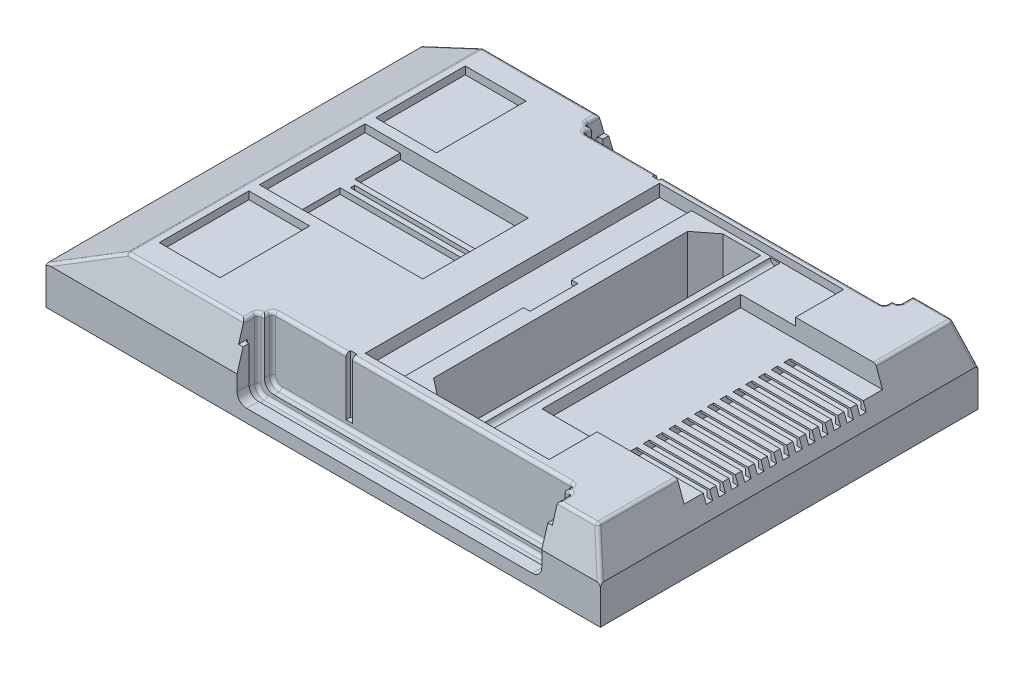
SolidWorks part; units mm, degrees
ref_plane "Front Plane" through (0, 0, 0) normal (0, 0, 1) x (1, 0, 0)
ref_plane "Top Plane" through (0, 0, 0) normal (0, 1, 0) x (1, 0, 0)
ref_plane "Right Plane" through (0, 0, 0) normal (1, 0, 0) x (0, 0, -1)
sketch "Sketch1" plane through (0, 0, 0) normal (0, 1, 0) x (1, 0, 0)
  line L1 (-219.964, -149.86) -> (0, -149.86)
  line L2 (-219.964, -149.86) -> (-219.964, 0)
  line L3 (-219.964, 0) -> (0, 0)
  line L4 (0, -149.86) -> (0, 0)
  dimension "D1" = 149.86
  dimension "D2" = 219.964
ref_plane "MiddleTop" through (0, 14.986, 0) normal (0, 1, 0) x (1, 0, 0)
sketch "Sketch2" plane through (0, 14.986, 0) normal (0, 1, 0) x (1, 0, 0)
  line L1 (0, 0) -> (-219.964, 0)
  line L2 (0, 0) -> (0, -149.86)
  line L3 (0, -149.86) -> (-219.964, -149.86)
  line L4 (-219.964, 0) -> (-219.964, -149.86)
extrude "Boss-Extrude1" add sketch "Sketch1" along normal blind 14.986
ref_plane "Plane2" through (0, 30.48, 0) normal (0, 1, 0) x (1, 0, 0)
sketch "Sketch3" plane through (0, 30.48, 0) normal (0, 1, 0) x (1, 0, 0)
  line L0 (0, -149.86) -> (-219.964, -149.86) construction
  line L1 (-192.024, -4.572) -> (-5.588, -4.572)
  line L2 (-192.024, -4.572) -> (-192.024, -145.288)
  line L3 (-192.024, -145.288) -> (-5.588, -145.288)
  line L4 (-5.588, -4.572) -> (-5.588, -145.288)
  line L5 (-219.964, 0) -> (-219.964, -149.86) construction
  line L6 (0, 0) -> (0, -149.86) construction
  dimension "D1" = 140.716
  dimension "D2" = 4.572
  dimension "D3" = 27.94
  dimension "D4" = 5.588
loft "Loft1" add profiles "Sketch2", "Sketch3" connector at (-219.964, 14.986, 149.86) connector at (-192.024, 30.48, 145.288)
sketch "Sketch4" plane through (0, 30.48, 0) normal (0, 1, 0) x (1, 0, 0)
  line L0 (-192.024, -145.288) -> (-5.588, -145.288) construction
  line L1 (-189.23, -135.636) -> (-165.1, -135.636)
  line L2 (-189.23, -135.636) -> (-189.23, -100.076)
  line L3 (-189.23, -100.076) -> (-165.1, -100.076)
  line L4 (-165.1, -135.636) -> (-165.1, -100.076)
  line L5 (-192.024, -4.572) -> (-192.024, -145.288) construction
  line L6 (-5.588, -4.572) -> (-192.024, -4.572) construction
  line L7 (-189.23, -49.784) -> (-165.1, -49.784)
  line L8 (-189.23, -49.784) -> (-189.23, -14.224)
  line L9 (-189.23, -14.224) -> (-165.1, -14.224)
  line L10 (-165.1, -49.784) -> (-165.1, -14.224)
  point P12 (-177.165, -14.224)
  dimension "D1" = 35.56
  dimension "D2" = 24.13
  dimension "D3" = 9.652
  dimension "D4" = 2.794
  dimension "D5" = 24.13
  dimension "D6" = 35.56
  dimension "D7" = 2.794
  dimension "D8" = 9.652
sketch "Sketch5" plane through (0, 30.48, 0) normal (0, 1, 0) x (1, 0, 0)
  line L0 (-189.23, -100.076) -> (-165.1, -100.076) construction
  line L1 (-189.23, -95.885) -> (-124.46, -95.885)
  line L2 (-189.23, -95.885) -> (-189.23, -53.975)
  line L3 (-189.23, -53.975) -> (-124.46, -53.975)
  line L4 (-124.46, -95.885) -> (-124.46, -53.975)
  line L5 (-192.024, -4.572) -> (-192.024, -145.288) construction
  dimension "D1" = 41.91
  dimension "D2" = 4.191
  dimension "D3" = 2.794
  dimension "D4" = 64.77
extrude "Cut-Extrude1" cut sketch "Sketch4" against normal blind 3.048
extrude "Cut-Extrude2" cut sketch "Sketch5" against normal blind 3.048
ref_plane "Plane3" through (0, 25.146, 0) normal (0, 1, 0) x (1, 0, 0)
sketch "Sketch6" plane through (0, 25.146, 0) normal (0, 1, 0) x (1, 0, 0)
  line L0 (-189.23, -53.975) -> (-189.23, -95.885) construction
  line L1 (-175.26, -72.0598) -> (-124.46, -72.0598)
  line L2 (-175.26, -72.0598) -> (-175.26, -77.851)
  line L3 (-175.26, -77.851) -> (-124.46, -77.851)
  line L4 (-124.46, -72.0598) -> (-124.46, -77.851)
  line L5 (-189.23, -95.885) -> (-124.46, -95.885) construction
  dimension "D1" = 50.8
  dimension "D2" = 13.97
  dimension "D3" = 5.7912
  dimension "D4" = 18.034
sketch "Sketch10" plane through (0, 30.48, 0) normal (0, 1, 0) x (1, 0, 0)
  line L6 (-219.964, -149.86) -> (0, -149.86) construction
  line L9 (-144.145, -145.1356) -> (-145.923, -145.1356)
  line L10 (-145.923, -145.1356) -> (-145.923, -139.8016)
  line L11 (-145.923, -139.8016) -> (-143.383, -139.8016)
  line L12 (-143.383, -139.8016) -> (-143.383, -136.5758)
  line L13 (-143.383, -136.5758) -> (-24.003, -136.5758)
  line L14 (-24.003, -136.5758) -> (-24.003, -139.8016)
  line L15 (-24.003, -139.8016) -> (-21.463, -139.8016)
  line L16 (-21.463, -139.8016) -> (-21.463, -145.1356)
  line L17 (-21.463, -145.1356) -> (-23.241, -145.1356)
  line L21 (-23.241, -149.86) -> (-144.145, -149.86)
  line L22 (-144.145, -145.1356) -> (-144.145, -149.86)
  line L23 (-23.241, -145.1356) -> (-23.241, -149.86)
  line L24 (0, -149.86) -> (0, 0) construction
  line L25 (-219.964, -74.93) -> (-5.588, -74.93) construction
  line L27 (-219.964, 0) -> (-219.964, -149.86) construction
  line L28 (-5.588, -145.288) -> (-5.588, -4.572) construction
  line L29 (-21.463, -4.7244) -> (-23.241, -4.7244)
  line L30 (-21.463, -10.0584) -> (-21.463, -4.7244)
  line L31 (-24.003, -10.0584) -> (-21.463, -10.0584)
  line L32 (-24.003, -13.2842) -> (-24.003, -10.0584)
  line L33 (-143.383, -13.2842) -> (-24.003, -13.2842)
  line L34 (-143.383, -10.0584) -> (-143.383, -13.2842)
  line L35 (-145.923, -10.0584) -> (-143.383, -10.0584)
  line L36 (-145.923, -4.7244) -> (-145.923, -10.0584)
  line L37 (-144.145, -4.7244) -> (-145.923, -4.7244)
  line L38 (-144.145, -4.7244) -> (-144.145, 0)
  line L39 (-23.241, 0) -> (-144.145, 0)
  line L40 (-23.241, -4.7244) -> (-23.241, 0)
  dimension "D1" = 13.2842
  dimension "D2" = 5.334
  dimension "D3" = 3.2258
  dimension "D4" = 2.54
  dimension "D5" = 124.46
  dimension "D6" = 3.2258
  dimension "D7" = 2.54
  dimension "D8" = 1.778
  dimension "D9" = 5.334
  dimension "D10" = 21.463
  dimension "D11" = 1.778
sketch "Sketch12" plane through (0, 30.48, 0) normal (0, 1, 0) x (1, 0, 0)
  line L1 (-145.923, -10.0584) -> (-21.463, -10.0584)
  line L2 (-145.923, -10.0584) -> (-145.923, -4.7244)
  line L3 (-145.923, -4.7244) -> (-21.463, -4.7244)
  line L4 (-21.463, -10.0584) -> (-21.463, -4.7244)
  line L5 (-145.923, -145.1356) -> (-21.463, -145.1356)
  line L6 (-145.923, -145.1356) -> (-145.923, -139.8016)
  line L7 (-145.923, -139.8016) -> (-21.463, -139.8016)
  line L8 (-21.463, -145.1356) -> (-21.463, -139.8016)
extrude "Cut-Extrude4" cut sketch "Sketch12" against normal blind 27.94
extrude "Cut-Extrude5" cut sketch "Sketch10" against normal blind 25.4
sketch "Sketch14" plane through (0, 30.48, 0) normal (0, 1, 0) x (1, 0, 0)
  line L1 (-145.923, -145.1356) -> (-144.145, -145.1356)
  line L2 (-145.923, -145.1356) -> (-145.923, -149.86)
  line L3 (-145.923, -149.86) -> (-144.145, -149.86)
  line L4 (-144.145, -145.1356) -> (-144.145, -149.86)
  line L5 (-21.463, -145.1356) -> (-23.241, -145.1356)
  line L6 (-21.463, -145.1356) -> (-21.463, -149.86)
  line L7 (-21.463, -149.86) -> (-23.241, -149.86)
  line L8 (-23.241, -145.1356) -> (-23.241, -149.86)
  line L9 (-145.923, -4.7244) -> (-144.145, -4.7244)
  line L10 (-145.923, -4.7244) -> (-145.923, 0)
  line L11 (-145.923, 0) -> (-144.145, 0)
  line L12 (-144.145, -4.7244) -> (-144.145, 0)
  line L13 (-21.463, -4.7244) -> (-23.241, -4.7244)
  line L14 (-21.463, -4.7244) -> (-21.463, 0)
  line L15 (-21.463, 0) -> (-23.241, 0)
  line L16 (-23.241, -4.7244) -> (-23.241, 0)
extrude "Cut-Extrude6" cut sketch "Sketch14" against normal blind 7.366
sketch "Sketch15" plane through (0, 30.48, 0) normal (0, 1, 0) x (1, 0, 0)
  line L0 (-5.588, -145.288) -> (-5.588, -4.572) construction
  line L1 (-110.363, -16.002) -> (-37.338, -16.002)
  line L2 (-110.363, -16.002) -> (-110.363, -132.842)
  line L3 (-110.363, -132.842) -> (-37.338, -132.842)
  line L4 (-37.338, -16.002) -> (-37.338, -35.052)
  line L5 (-5.588, -4.572) -> (-21.463, -4.572) construction
  line L6 (-37.338, -35.052) -> (-59.182, -35.052)
  line L7 (-59.182, -35.052) -> (-59.182, -113.792)
  line L8 (-59.182, -113.792) -> (-37.338, -113.792)
  line L9 (-37.338, -113.792) -> (-37.338, -132.842)
  dimension "D1" = 73.025
  dimension "D2" = 31.75
  dimension "D3" = 116.84
  dimension "D4" = 11.43
  dimension "D5" = 21.844
  dimension "D6" = 78.74
  dimension "D7" = 19.05
extrude "Cut-Extrude7" cut sketch "Sketch15" against normal blind 3.048
sketch "Sketch16" plane through (0, 30.48, 0) normal (0, 1, 0) x (1, 0, 0)
  line L1 (-59.182, -35.052) -> (0.508, -35.052)
  line L2 (-59.182, -35.052) -> (-59.182, -113.792)
  line L3 (-59.182, -113.792) -> (0.508, -113.792)
  line L4 (0.508, -35.052) -> (0.508, -113.792)
  point P7 (0, 0)
  point P9 (0, 0)
  dimension "D1" = 59.69
extrude "Cut-Extrude8" cut sketch "Sketch16" against normal blind 7.62
sketch "Sketch17" plane through (0, 30.48, 0) normal (0, 1, 0) x (1, 0, 0)
  line L0 (-110.363, -132.842) -> (-37.338, -132.842) construction
  line L1 (-110.363, -16.002) -> (-97.663, -16.002)
  line L2 (-110.363, -16.002) -> (-110.363, -132.842)
  line L3 (-110.363, -132.842) -> (-97.663, -132.842)
  line L4 (-97.663, -16.002) -> (-97.663, -63.627)
  line L5 (-97.663, -63.627) -> (-95.123, -63.627)
  line L6 (-95.123, -63.627) -> (-95.123, -82.677)
  line L7 (-95.123, -82.677) -> (-97.663, -82.677)
  line L8 (-97.663, -82.677) -> (-97.663, -132.842)
  dimension "D1" = 12.7
  dimension "D2" = 19.05
  dimension "D3" = 47.625
  dimension "D4" = 2.54
extrude "Cut-Extrude9" cut sketch "Sketch17" against normal blind 4.826
sketch "Sketch18" plane through (0, 30.48, 0) normal (0, 1, 0) x (1, 0, 0)
  line L0 (-83.5048, -17.78) -> (-91.313, -23.876)
  line L1 (-83.5048, -17.78) -> (-68.5188, -17.78)
  line L2 (-91.313, -23.876) -> (-91.313, -124.714)
  line L3 (-83.5048, -130.81) -> (-68.5188, -130.81)
  line L4 (-68.5188, -17.78) -> (-68.5188, -130.81)
  line L5 (-83.5048, -130.81) -> (-91.313, -124.714)
  line L6 (-97.663, -132.842) -> (-37.338, -132.842) construction
  line L8 (-95.123, -82.677) -> (-95.123, -63.627) construction
  dimension "D1" = 14.986
  dimension "D2" = 9.906
  dimension "D3" = 9.906
  dimension "D4" = 14.986
  dimension "D5" = 100.838
  dimension "D6" = 113.03
  dimension "D7" = 2.032
  dimension "D8" = 3.81
extrude "Cut-Extrude10" cut sketch "Sketch18" against normal through all
sketch "Sketch19" plane through (0, 30.48, 0) normal (0, 1, 0) x (1, 0, 0)
  line L0 (0, -149.86) -> (0, 0) construction
  line L1 (-31.75, -42.672) -> (0, -42.672)
  line L2 (-31.75, -42.672) -> (-31.75, -45.212)
  line L3 (-31.75, -45.212) -> (0, -45.212)
  line L4 (0, -42.672) -> (0, -45.212)
  line L5 (-2.8398, -35.052) -> (-59.182, -35.052) construction
  dimension "D1" = 2.54
  dimension "D2" = 31.75
  dimension "D3" = 7.62
extrude "Cut-Extrude11" cut sketch "Sketch19" against normal blind 10.922
pattern_linear "LPattern1" count 13 spacing 5.08 along (0, 0, 1) of "Cut-Extrude11"
ref_plane "Plane5" through (0, 0, 103.632) normal (0, 0, 1) x (1, 0, 0)
sketch "Sketch20" plane through (0, 0, 103.632) normal (0, 0, 1) x (1, 0, 0)
  line L0 (-2.8398, 22.86) -> (-31.75, 22.86) construction
  line L1 (-31.75, 22.098) -> (-3.81, 22.098)
  line L2 (-31.75, 22.098) -> (-31.75, 19.558)
  line L3 (-31.75, 19.558) -> (-3.81, 19.558)
  line L4 (-3.81, 22.098) -> (-3.81, 19.558)
  line L6 (-31.75, 19.558) -> (-31.75, 22.86) construction
  dimension "D1" = 0.762
  dimension "D2" = 2.54
  dimension "D3" = 0
  dimension "D4" = 27.94
extrude "Cut-Extrude12" cut sketch "Sketch20" against normal blind 63.5
sketch "Sketch25" plane through (0, 30.48, 0) normal (0, 1, 0) x (1, 0, 0)
  line L1 (-175.26, -72.0598) -> (-124.46, -72.0598)
  line L2 (-175.26, -72.0598) -> (-175.26, -53.975)
  line L3 (-175.26, -53.975) -> (-124.46, -53.975)
  line L4 (-124.46, -72.0598) -> (-124.46, -53.975)
  line L5 (-175.26, -77.851) -> (-124.46, -77.851)
  line L6 (-175.26, -77.851) -> (-175.26, -95.885)
  line L7 (-175.26, -95.885) -> (-124.46, -95.885)
  line L8 (-124.46, -77.851) -> (-124.46, -95.885)
extrude "Cut-Extrude14" cut sketch "Sketch25" against normal blind 5.334
sketch "Sketch21" plane through (0, 30.48, 0) normal (0, 1, 0) x (1, 0, 0)
  line L1 (-173.228, -74.0918) -> (-126.238, -74.0918)
  line L2 (-173.228, -74.0918) -> (-173.228, -75.819)
  line L3 (-173.228, -75.819) -> (-126.238, -75.819)
  line L4 (-126.238, -74.0918) -> (-126.238, -75.819)
  line L7 (-124.46, -53.975) -> (-189.23, -53.975) construction
  line L8 (-175.26, -95.885) -> (-124.46, -95.885) construction
  line L9 (-124.46, -95.885) -> (-124.46, -53.975) construction
  dimension "D1" = 20.1168
  dimension "D2" = 20.066
  dimension "D3" = 46.99
  dimension "D4" = 1.778
extrude "Cut-Extrude13" cut sketch "Sketch21" against normal through all
ref_plane "Plane6" through (0, 0, 16.51) normal (0, 0, 1) x (1, 0, 0)
sketch "Sketch26" plane through (0, 0, 16.51) normal (0, 0, 1) x (1, 0, 0)
  line L2 (-37.338, 27.432) -> (-97.663, 27.432) construction
  circle A0 centre (-64.008, 27.432) radius 1.905
  dimension "D3" = 3.81
  dimension "D1" = 0
  dimension "D2" = 58.42
extrude "Cut-Extrude15" cut sketch "Sketch26" along normal blind 115.57
fillet "Fillet1" radius 3.81 12 edges at (-144.145, 5.08, 2.3622) (-23.241, 5.08, 2.3622) (-144.145, 5.08, 147.4978) (-23.241, 5.08, 147.4978) (-24.003, 5.08, 138.1887) (-143.383, 5.08, 138.1887) (-143.383, 5.08, 11.6713) (-24.003, 5.08, 11.6713) (-21.463, 2.54, 142.4686) (-145.923, 2.54, 142.4686) (-145.923, 2.54, 7.3914) (-21.463, 2.54, 7.3914)
fillet "Fillet2" radius 1.27 30 edges at (-145.923, 14.732, 4.7244) (-144.8071, 3.6559, 4.7244) (-83.693, 2.54, 4.7244) (-22.5789, 3.6559, 4.7244) (-21.463, 18.415, 10.0584) (-145.923, 18.415, 10.0584) (-144.8071, 3.6559, 10.0584) (-83.693, 2.54, 10.0584) (-24.003, 19.685, 13.2842) (-143.383, 19.685, 13.2842) (-142.2671, 6.1959, 13.2842) (-83.693, 5.08, 13.2842) (-24.003, 19.685, 136.5758) (-25.1189, 6.1959, 136.5758) (-143.383, 19.685, 136.5758) (-142.2671, 6.1959, 136.5758) (-21.463, 18.415, 139.8016) (-22.5789, 3.6559, 139.8016) (-83.693, 2.54, 139.8016) (-144.8071, 3.6559, 139.8016) (-21.463, 14.732, 145.1356) (-22.5789, 3.6559, 145.1356) (-83.693, 2.54, 145.1356) (-144.8071, 3.6559, 145.1356) (-21.463, 14.732, 4.7244) (-22.5789, 3.6559, 10.0584) (-25.1189, 6.1959, 13.2842) (-83.693, 5.08, 136.5758) (-145.923, 18.415, 139.8016) (-145.923, 14.732, 145.1356)
fillet "Fillet3" radius 1.27 33 edges at (-23.368, 30.48, 139.8016) (-21.835, 30.48, 140.1736) (-23.368, 30.48, 10.0584) (-21.835, 30.48, 9.6864) (-144.018, 30.48, 10.0584) (-145.551, 30.48, 9.6864) (-144.018, 30.48, 139.8016) (-145.551, 30.48, 140.1736) (-143.383, 30.48, 11.0363) (-143.011, 30.48, 12.9122) (-24.003, 30.48, 11.0363) (-24.375, 30.48, 12.9122) (-24.003, 30.48, 138.8237) (-24.375, 30.48, 136.9478) (-143.383, 30.48, 138.8237) (-143.011, 30.48, 136.9478) (-83.693, 30.48, 13.2842) (-83.693, 30.48, 136.5758)
sketch "Sketch27" plane through (0, 30.48, 0) normal (0, 1, 0) x (1, 0, 0)
  line L0 (-139.573, -136.5758) -> (-27.813, -136.5758) construction
  line L1 (-114.173, -134.7978) -> (-111.633, -134.7978)
  line L2 (-114.173, -134.7978) -> (-114.173, -136.5758)
  line L3 (-114.173, -136.5758) -> (-111.633, -136.5758)
  line L4 (-111.633, -134.7978) -> (-111.633, -136.5758)
  line L5 (-145.923, -143.8656) -> (-145.923, -141.0716) construction
  line L6 (0, -74.93) -> (-226.7454, -74.93) construction
  line L8 (0, -148.663) -> (0, -1.197) construction
  point P12 (0, 0)
  dimension "D1" = 1.778
  dimension "D2" = 2.54
  dimension "D3" = 31.75
sketch "Sketch28" plane through (0, 30.48, 0) normal (0, 1, 0) x (1, 0, 0)
  line L2 (-114.173, -13.2842) -> (-114.173, -15.0622)
  line L3 (-114.173, -15.0622) -> (-111.633, -15.0622)
  line L4 (-111.633, -13.2842) -> (-111.633, -15.0622)
  line L5 (-145.923, -4.1972) -> (-145.923, -8.7884) construction
  line L8 (-114.173, -13.2842) -> (-111.633, -13.2842)
  line L9 (-142.113, -13.2842) -> (-25.273, -13.2842) construction
  dimension "D1" = 1.778
  dimension "D2" = 2.54
  dimension "D3" = 31.75
  dimension "D4" = 0
extrude "Cut-Extrude16" cut sketch "Sketch27" against normal blind 22.86
extrude "Cut-Extrude17" cut sketch "Sketch28" against normal blind 22.86
